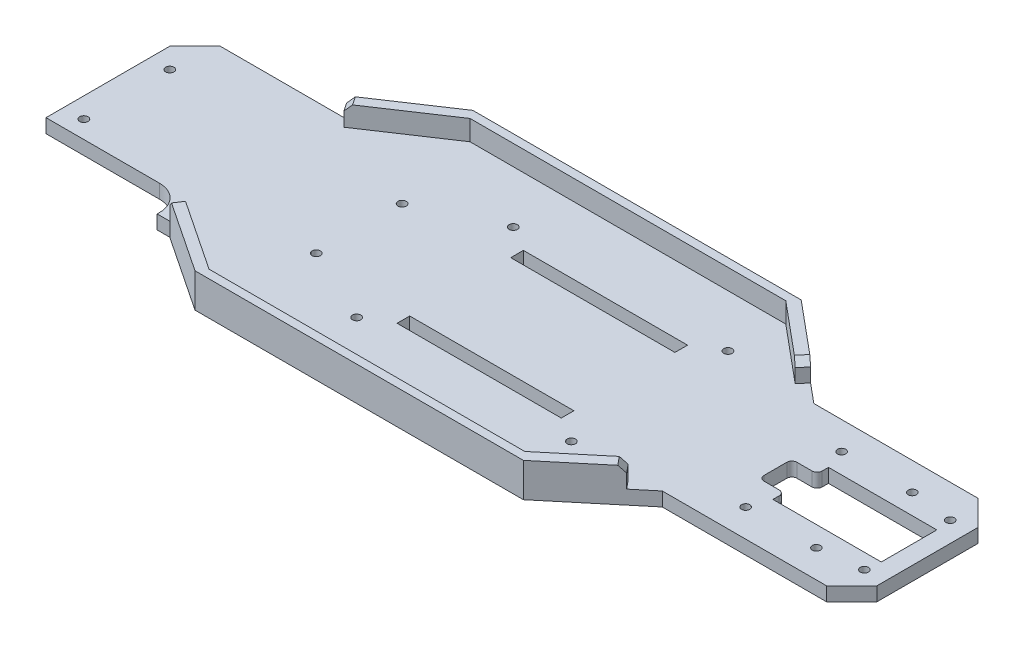
SolidWorks part; units mm, degrees
material "PETG - Polymaker"
ref_plane "Front Plane" through (0, 0, 0) normal (0, 0, 1) x (1, 0, 0)
ref_plane "Top Plane" through (0, 0, 0) normal (0, 1, 0) x (1, 0, 0)
ref_plane "Right Plane" through (0, 0, 0) normal (1, 0, 0) x (0, 0, -1)
sketch "Sketch1" plane through (0, 0, 0) normal (0, 1, 0) x (1, 0, 0)
  line L0 (-235.1499, 0) -> (235.1499, 0) construction
  line L1 (0, 0) -> (0, 52596.8311) construction
  line L2 (-95, 35) -> (-65, 55)
  line L3 (-65, 55) -> (65, 55)
  line L4 (-95, 35) -> (-155, 35)
  line L5 (-155, 35) -> (-155, -35)
  line L6 (-65, -55) -> (65, -55)
  line L7 (-95, -35) -> (-65, -55)
  line L8 (-95, -35) -> (-155, -35)
  line L9 (65, 55) -> (95, 30)
  line L10 (95, 30) -> (170, 30)
  line L11 (170, 30) -> (170, -30)
  line L12 (95, -30) -> (170, -30)
  line L13 (65, -55) -> (95, -30)
  point P3 (0, 0)
  point P10 (-80, 45)
  point P15 (-80, -45)
  point P18 (-155, 0)
  point P19 (0, -55)
  point P20 (0, 55)
  point P23 (170, 0)
  dimension "D1" = 55
  dimension "D2" = 70
  dimension "D3" = 30
  dimension "D4" = 60
  dimension "D5" = 130
  dimension "D6" = 75
  dimension "D7" = 60
  dimension "D8" = 30
  dimension "D9" = 110
extrude "Boss-Extrude1" add sketch "Sketch1" along normal blind 5.5
sketch "Sketch3" plane through (0, 5.5, 0) normal (0, 1, 0) x (1, 0, 0)
  line L0 (0, 0) -> (50000, 0) construction
  line L1 (0, 0) -> (0, 50000) construction
  line L2 (0, 55) -> (-65, 55)
  line L3 (65, 55) -> (-65, 55) construction
  line L4 (-65, 55) -> (-95, 35)
  line L5 (-95, 35) -> (-92.7812, 31.6718)
  line L6 (-92.7812, 31.6718) -> (-62.7812, 51.6718)
  line L7 (-62.7812, 51.6718) -> (0, 51.6718)
  line L8 (-65, 55) -> (-62.7812, 51.6718) construction
  line L9 (0, 55) -> (65, 55)
  line L10 (65, 55) -> (87.3178, 36.4018)
  line L11 (87.3178, 36.4018) -> (84.5443, 33.0736)
  line L12 (84.5443, 33.0736) -> (62.2265, 51.6718)
  line L13 (62.2265, 51.6718) -> (0, 51.6718)
  line L14 (62.2265, 51.6718) -> (65, 55) construction
  line L15 (62.2265, -51.6718) -> (65, -55) construction
  line L16 (-65, -55) -> (-62.7812, -51.6718) construction
  line L27 (-65, 55) -> (-95, 35) construction
  line L28 (95, 30) -> (65, 55) construction
  line L29 (62.2265, -51.6718) -> (0, -51.6718)
  line L30 (84.5443, -33.0736) -> (62.2265, -51.6718)
  line L31 (87.3178, -36.4018) -> (84.5443, -33.0736)
  line L32 (65, -55) -> (87.3178, -36.4018)
  line L33 (0, -55) -> (65, -55)
  line L34 (-62.7812, -51.6718) -> (0, -51.6718)
  line L35 (-92.7812, -31.6718) -> (-62.7812, -51.6718)
  line L36 (-95, -35) -> (-92.7812, -31.6718)
  line L37 (-65, -55) -> (-95, -35)
  line L38 (0, -55) -> (-65, -55)
  dimension "D1" = 4
  dimension "D2" = 0
  dimension "D3" = 10
extrude "Chassis-Walls1" add sketch "Sketch3" along normal blind 8
chamfer "Chamfer1" distance 10 angle 45 2 edges at (-155, 2.75, -35) (-155, 2.75, 35)
chamfer "Chamfer2" distance 10 angle 45 2 edges at (170, 2.75, -30) (170, 2.75, 30)
chamfer "Chamfer3" distance 2.5 angle 45 4 edges at (-93.8906, 13.5, -33.3359) (85.931, 13.5, -34.7377) (-93.8906, 13.5, 33.3359) (85.931, 13.5, 34.7377)
sketch "Sketch4" plane through (0, 0, 0) normal (0, -1, 0) x (1, 0, 0)
  line L0 (0, 0) -> (50000, 0) construction
  line L1 (-147, 17) -> (-55, 17) construction
  line L2 (-155, -25) -> (-155, 25) construction
  circle A0 centre (-147, 17) radius 1.65
  circle A1 centre (-55, 17) radius 1.65
  circle A2 centre (-55, -17) radius 1.65
  circle A3 centre (-147, -17) radius 1.65
  circle A4 centre (-25, 31) radius 1.65
  circle A5 centre (60, 31) radius 1.65
  circle A6 centre (60, -31) radius 1.65
  circle A7 centre (-25, -31) radius 1.65
  dimension "D1" = 3.3
  dimension "D2" = 3.3
  dimension "D6" = 3.3
  dimension "D8" = 3.3
  dimension "D3" = 8
  dimension "D4" = 92
  dimension "D5" = 34
  dimension "D7" = 30
  dimension "D9" = 85
  dimension "D10" = 62
extrude "Cut-Extrude1" cut sketch "Sketch4" against normal blind 10
sketch "Sketch5" plane through (0, 5.5, 0) normal (0, 1, 0) x (1, 0, 0)
  line L0 (-155, -24) -> (-100, -24)
  line L1 (-155, 25) -> (-155, -25) construction
  line L2 (-100, -24) -> (-100, -35)
  line L3 (-145, -35) -> (-95, -35) construction
  line L4 (-100, -35) -> (-155, -35)
  line L5 (-155, -35) -> (-155, -24)
  dimension "D1" = 55
  dimension "D2" = 11
extrude "Cut-Extrude2" cut sketch "Sketch5" against normal blind 10
sketch "Sketch6" plane through (0, 5.5, 0) normal (0, 1, 0) x (1, 0, 0)
  line L0 (0, 0) -> (50000, 0) construction
  line L1 (60, 31) -> (-25, 31) construction
  line L2 (17.5, 30.75) -> (17.5, 50030.75) construction
  line L3 (-15, -20) -> (50, -25) construction
  line L4 (-15, 25) -> (50, 25)
  line L5 (-15, 25) -> (-15, 20)
  line L6 (-15, 20) -> (50, 20)
  line L7 (50, 25) -> (50, 20)
  line L8 (-15, 25) -> (50, 20) construction
  line L9 (-15, 20) -> (50, 25) construction
  line L10 (-15, -25) -> (50, -20) construction
  line L11 (50, -25) -> (50, -20)
  line L12 (-15, -20) -> (50, -20)
  line L13 (-15, -25) -> (-15, -20)
  line L14 (-15, -25) -> (50, -25)
  point P9 (17.5, 31)
  point P10 (17.5, 22.5)
  point P19 (17.5, -22.5)
  dimension "D1" = 5
  dimension "D2" = 65
  dimension "D3" = 20
extrude "Cut-Extrude3" cut sketch "Sketch6" against normal through all
fillet "Fillet1" radius 10 1 edges at (-100, 2.75, 24)
sketch "Sketch7" plane through (0, 5.5, 0) normal (0, 1, 0) x (1, 0, 0)
  line L0 (175, 0) -> (50175, 0) construction
  line L1 (170, -20) -> (170, 20) construction
  line L3 (120.8, 10) -> (161.7, 10) construction
  line L4 (120.8, 10) -> (120.8, -10) construction
  line L5 (120.8, -10) -> (161.7, -10) construction
  line L6 (161.7, 10) -> (161.7, -10) construction
  line L7 (120.8, 10) -> (161.7, -10) construction
  line L8 (120.8, -10) -> (161.7, 10) construction
  line L9 (119.8, 11) -> (162.7, 11)
  line L10 (119.8, 11) -> (119.8, -11)
  line L11 (119.8, -11) -> (162.7, -11)
  line L12 (162.7, 11) -> (162.7, -11)
  line L13 (119.8, 11) -> (162.7, -11) construction
  line L14 (119.8, -11) -> (162.7, 11) construction
  point P4 (170, 0)
  point P5 (141.25, 0)
  point P10 (141.25, 0)
  dimension "D1" = 20
  dimension "D2" = 40.9
  dimension "D3" = 1
  dimension "D4" = 1
  dimension "D5" = 8.3
extrude "Cut-Extrude4" cut sketch "Sketch7" against normal through all
sketch "Sketch9" plane through (0, 5.5, 0) normal (0, 1, 0) x (1, 0, 0)
  circle A0 centre (117, -19) radius 1.625
  circle A1 centre (145, -19) radius 1.625
  circle A2 centre (162, -17) radius 1.625
  dimension "D1" = 3.25
  dimension "D2" = 3.25
  dimension "D3" = 3.25
extrude "Cut-Extrude5" cut sketch "Sketch9" against normal through all
mirror "Mirror1" about plane through (0, 0, 0) normal (0, 0, 1) of "Cut-Extrude5"
sketch "Sketch10" plane through (0, 5.5, 0) normal (0, 1, 0) x (1, 0, 0)
  line L0 (124.8, 0) -> (50124.8, 0) construction
  line L1 (119.8, 11) -> (119.8, -11) construction
  line L2 (119.8, 6.5) -> (109.8, 6.5)
  line L3 (109.8, 6.5) -> (109.8, -6.5)
  line L4 (119.8, 6.5) -> (119.8, -6.5)
  line L5 (119.8, -6.5) -> (109.8, -6.5)
  point P4 (119.8, 0)
  point P10 (119.8, 0)
  point P11 (109.8, 0)
  dimension "D1" = 13
  dimension "D2" = 10
extrude "Servo-Cable-Cutout" cut sketch "Sketch10" against normal blind 10
fillet "Fillet2" radius 2 4 edges at (119.8, 2.75, -6.5) (119.8, 2.75, 6.5) (109.8, 2.75, 6.5) (109.8, 2.75, -6.5)
equation "\"D6@Sketch4\"=\"D2@Sketch4\""
equation "\"D8@Sketch4\"=\"D2@Sketch4\""
equation "\"D2@Sketch4\"=\"D1@Sketch4\""
equation "\"D2@Sketch9\"=\"D1@Sketch9\""
equation "\"D3@Sketch9\"=\"D1@Sketch9\""
